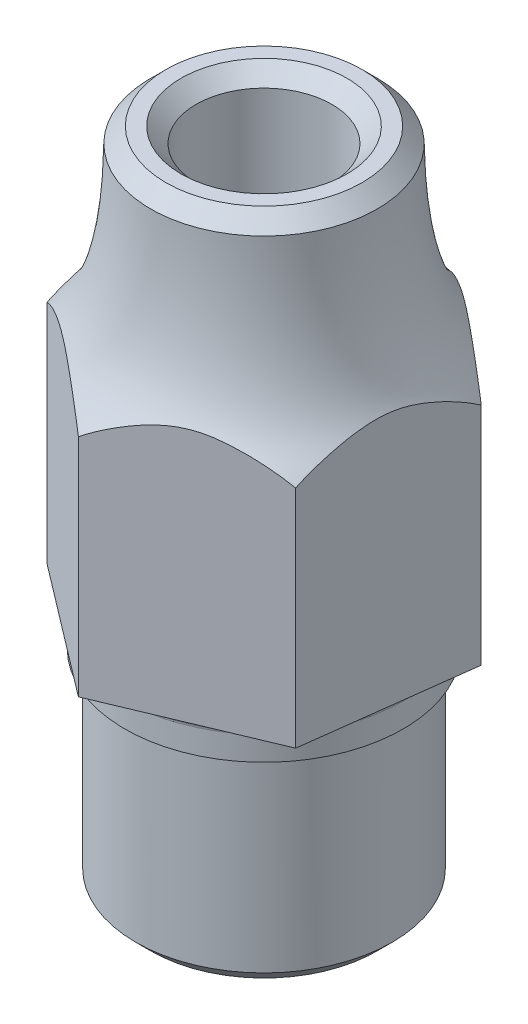
SolidWorks part; units mm, degrees
material "Acier allié inoxydable"
ref_plane "Plan de face" through (0, 0, 0) normal (0, 0, 1) x (1, 0, 0)
ref_plane "Plan de dessus" through (0, 0, 0) normal (0, 1, 0) x (1, 0, 0)
ref_plane "Plan de droite" through (0, 0, 0) normal (1, 0, 0) x (0, 0, -1)
sketch "Esquisse1" plane through (0, 0, 0) normal (0, 1, 0) x (1, 0, 0)
  circle A0 centre (0, 0) radius 4.25
  dimension "D1" = 8.5
extrude "Boss.-Extru.1" add sketch "Esquisse1" along normal blind 7.8
sketch "Esquisse2" plane through (0, 7.8, 0) normal (0, 1, 0) x (1, 0, 0)
  circle A0 centre (0, 0) radius 5.5
  dimension "D1" = 11
extrude "Boss.-Extru.2" add sketch "Esquisse2" along normal blind 14
sketch "Esquisse3" plane through (0, 21.8, 0) normal (0, 1, 0) x (1, 0, 0)
  line L1 (-0.6941, -5.456) -> (4.378, -3.3291)
  line L2 (4.378, -3.3291) -> (5.0721, 2.1269)
  line L3 (5.0721, 2.1269) -> (0.6941, 5.456)
  line L4 (0.6941, 5.456) -> (-4.378, 3.3291)
  line L5 (-4.378, 3.3291) -> (-5.0721, -2.1269)
  line L6 (-5.0721, -2.1269) -> (-0.6941, -5.456)
  circle A0 centre (0, 0) radius 4.7631 construction
extrude "Enlèv. mat.-Extru.1" cut sketch "Esquisse3" against normal blind 14 flip side to cut
sketch "Esquisse4" plane through (0, 0, 0) normal (0, 0, 1) x (1, 0, 0)
  line L0 (-0.6941, 21.8) -> (4.378, 21.8) construction
  line L2 (3.75, 19.4771) -> (3.75, 24.1229) construction
  line L3 (0, 0) -> (0, 21.8) construction
  line L4 (5.0721, 7.8) -> (5.0721, 21.8) construction
  line L5 (6.9079, 13.4166) -> (8.0378, 13.4166)
  line L6 (8.0378, 13.4166) -> (8.0378, 21.8)
  line L7 (8.0378, 21.8) -> (3.75, 21.8)
  spline S0 degree 3 poles (3.75, 21.8) (3.75, 20.2592) (3.8667, 17.1839) (5.9831, 14.7468) (6.3409, 13.9401) (6.9079, 13.4166) knots 0 0 0 0 0.502926 0.602926 1 1 1 1
  dimension "D1" = 8.3834
  dimension "D2" = 3.75
  dimension "D3" = 6
revolve "Enlèvement de matière-Révolution1" cut sketch "Esquisse4" angle 360 about L3
sketch "Esquisse5" plane through (0, 21.8, 0) normal (0, 1, 0) x (1, 0, 0)
  circle A0 centre (0, 0) radius 2.25
  dimension "D1" = 4.5
extrude "Enlèv. mat.-Extru.2" cut sketch "Esquisse5" against normal blind 20
sketch "Esquisse6" plane through (0, 0, 0) normal (0, -1, 0) x (1, 0, 0)
  line L1 (-1.1828, 1.3032) -> (-1.72, -0.3727)
  line L2 (-1.72, -0.3727) -> (-0.5372, -1.6759)
  line L3 (-0.5372, -1.6759) -> (1.1828, -1.3032)
  line L4 (1.1828, -1.3032) -> (1.72, 0.3727)
  line L5 (1.72, 0.3727) -> (0.5372, 1.6759)
  line L6 (0.5372, 1.6759) -> (-1.1828, 1.3032)
  circle A0 centre (0, 0) radius 1.5241 construction
  dimension "D1" = 3.44
extrude "Enlèv. mat.-Extru.3" cut sketch "Esquisse6" against normal blind 20
sketch "Esquisse7" plane through (0, 7.8, 0) normal (0, -1, 0) x (1, 0, 0)
  circle A0 centre (0, 0) radius 4.6108
extrude "Boss.-Extru.3" add sketch "Esquisse7" along normal blind 1
chamfer "Chanfrein1" distance 0.5 angle 45 3 edges at (0, 0, 4.25) (0, 21.8, 2.25) (0, 21.8, -3.75)
fillet "Congé1" radius 0.2 1 edges at (0, 7.8, 4.6108)
